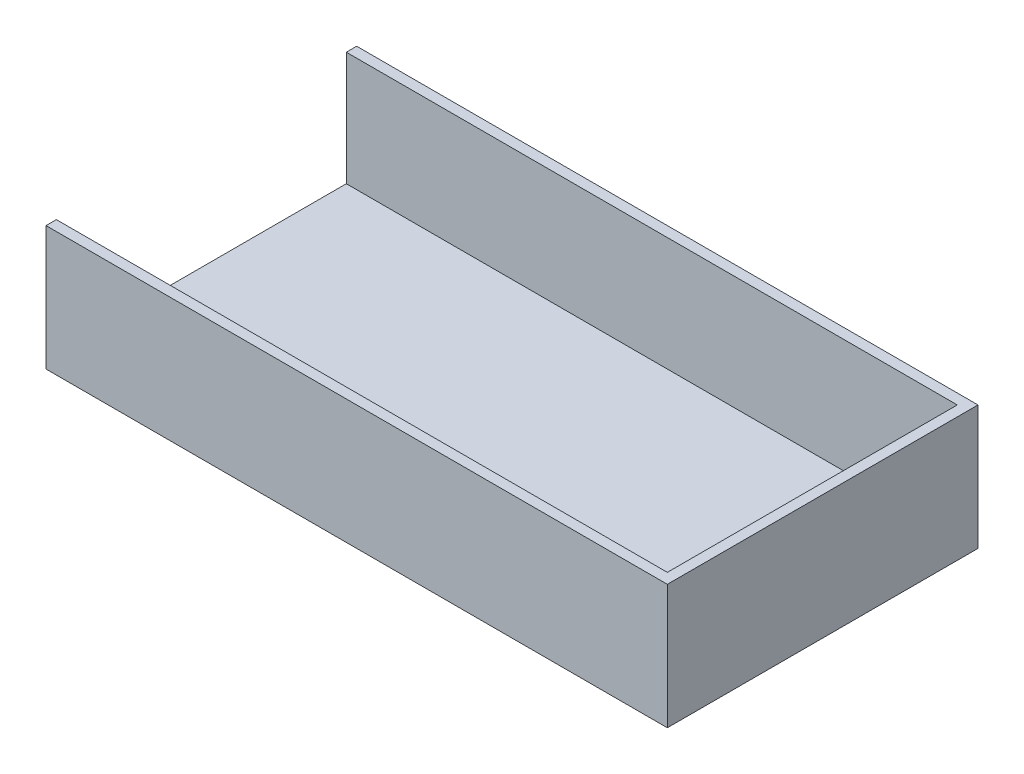
SolidWorks part; units mm, degrees
ref_plane "Front Plane" through (0, 0, 0) normal (0, 0, 1) x (1, 0, 0)
ref_plane "Top Plane" through (0, 0, 0) normal (0, 1, 0) x (1, 0, 0)
ref_plane "Right Plane" through (0, 0, 0) normal (1, 0, 0) x (0, 0, -1)
sketch "Sketch2" plane through (0, 0, 0) normal (0, 1, 0) x (1, 0, 0)
  line L0 (-72.5, 35) -> (-75, 35)
  line L1 (-75, 37.5) -> (75, 37.5)
  line L2 (-75, 37.5) -> (-75, -37.5)
  line L3 (-75, -37.5) -> (75, -37.5)
  line L4 (75, 37.5) -> (75, -37.5)
  line L5 (-75, 37.5) -> (75, -37.5) construction
  line L6 (-75, -37.5) -> (75, 37.5) construction
  line L7 (72.5, 35) -> (-72.5, 35)
  line L8 (72.5, 35) -> (72.5, -35)
  line L9 (72.5, -35) -> (-72.5, -35)
  line L10 (-72.5, 35) -> (-72.5, -35)
  line L11 (72.5, 35) -> (-72.5, -35) construction
  line L12 (72.5, -35) -> (-72.5, 35) construction
  line L13 (-72.5, -35) -> (-75, -35)
  point P0 (0, 0)
  point P6 (0, 0)
  dimension "D1" = 150
  dimension "D2" = 75
  dimension "D3" = 2.5
  dimension "D4" = 2.5
extrude "Boss-Extrude1" add sketch "Sketch2" along normal mid plane 30 contours L9 L13 L2 L3 L4 L1 L0 L7 L8 region at (-73.75, 0, -36.6771)
extrude "Boss-Extrude2" add sketch "Sketch2<3>" along normal blind 2.5 from surface contours L7 L10 L9 L8 | L13 L10 L0 L2 region at (-73.75, 0, 0) region at (0, 0, 0) starting at face at (-0.625, -15, 0)
sketch "Sketch2<3>" plane through (0, 0, 0) normal (0, 1, 0) x (1, 0, 0) same geometry as "Sketch2"
